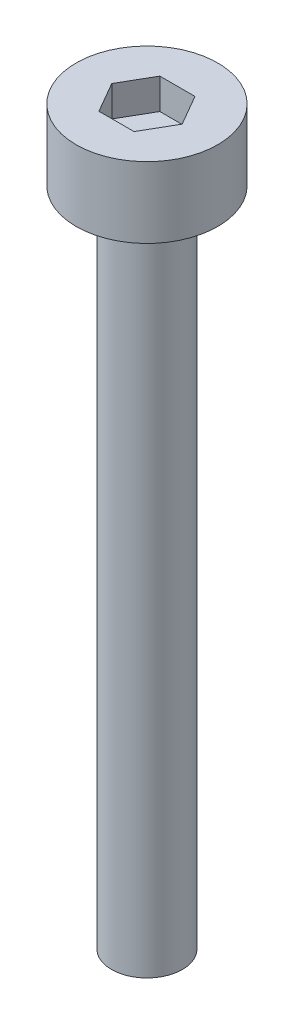
SolidWorks part; units mm, degrees
ref_plane "Front Plane" through (0, 0, 0) normal (0, 0, 1) x (1, 0, 0)
ref_plane "Top Plane" through (0, 0, 0) normal (0, 1, 0) x (1, 0, 0)
ref_plane "Right Plane" through (0, 0, 0) normal (1, 0, 0) x (0, 0, -1)
sketch "Sketch1" plane through (0, 0, 0) normal (0, 1, 0) x (1, 0, 0)
  circle A0 centre (0, 0) radius 1.5
  dimension "D1" = 3
extrude "ScrewShaft" add sketch "Sketch1" along normal blind 28
sketch "Sketch2" plane through (0, 28, 0) normal (0, 1, 0) x (1, 0, 0)
  circle A0 centre (0, 0) radius 3
  dimension "D1" = 6
extrude "Boss-Extrude2" add sketch "Sketch2" along normal blind 3
sketch "Sketch3" plane through (0, 31, 0) normal (0, 1, 0) x (1, 0, 0)
  line L0 (0, 0) -> (0, 1.29) construction
  line L1 (1.4896, 0) -> (0.7448, 1.29)
  line L2 (0.7448, 1.29) -> (-0.7448, 1.29)
  line L3 (-0.7448, 1.29) -> (-1.4896, 0)
  line L4 (-1.4896, 0) -> (-0.7448, -1.29)
  line L5 (-0.7448, -1.29) -> (0.7448, -1.29)
  line L6 (0.7448, -1.29) -> (1.4896, 0)
  circle A0 centre (0, 0) radius 1.29 construction
  dimension "D1" = 2.58
extrude "Cut-Extrude1" cut sketch "Sketch3" against normal blind 1.3
equation "\"X-ROD-SPACING\"=45"
equation "\"Y-ROD-SPACING\"=75"
equation "\"Z-ROD-SPACING\"=17.5"
equation "\"Y-BED-OFFSET\"=2"
equation "\"Y-BED-ROD-INSET\"=3.5"
equation "\"T-SLOT-NUT-FILLET-RADIUS\"=0.5"
equation "\"T-SLOT-SCREW-SHAFT-RADIUS\"=1.55"
equation "\"T-SLOT-SCREW-SHAFT-CUTOUT-LENGTH\"=11"
equation "\"T-SLOT-NUT-DEPTH\"=3.5"
equation "\"T-SLOT-NUT-WIDTH\"=2.85"
equation "\"T-SLOT-NUT-END-DISTANCE\"=8"
equation "\"ACRYLIC-THICKNESS\"=10"
equation "\"ACRYLIC-THICKNESS2\"=4.5"
equation "\"ACRYLIC-TAB-CUTOUT-SIZE\"=\"ACRYLIC-THICKNESS\"+\"ACRYLIC-TAB-TOLERANCE\"*2"
equation "\"ACRYLIC-TAB-WIDTH\"=\"ACRYLIC-THICKNESS\""
equation "\"ACRYLIC-M3-HOLE\"=2.9"
equation "\"SMOOTHROD-CAP-SCREW-DISTANCE\"=20"
equation "\"FRAME-WIDTH-INNER\"=370"
equation "\"NEMA17-HOLE-SPACING\"=31"
equation "\"NEMA17-CENTRAL-CUTOUT\"=22.5"
equation "\"Z-BRACKET-REACH\"=55"
equation "\"TOP-BRACKET-SPACING\"=40"
equation "\"SMOOTHROD-X-LENGTH\"=350"
equation "\"SMOOTHROD-Y-LENGTH\"=350"
equation "\"SMOOTHROD-Z-LENGTH\"=350"
equation "\"SMOOTHROD-TIGHTENING-HEADROOM\"=.25"
equation "\"LEADSCREW-Z-LENGTH\"=300"
equation "\"SCREW-LENGTH-FRAME\"=\"ACRYLIC-THICKNESS\" + 10"
equation "\"SCREW-HEAD-RADIUS\"=6"
equation "\"PRINTED-X-SMOOTHROD-DIAMETER\"=9.0"
equation "\"PRINTED-X-SMOOTHROD-CUTOUT\"=10"
equation "\"PRINTED-X-BASE-HEIGHT\"=10"
equation "\"PRINTED-LM8UU-CUTOUT-SIZE\"=15.5"
equation "\"PRINTED-LM8UU-CUTOUT-LENGTH\"=24.5"
equation "\"PRINTED-X-IDLER-HEIGHT\"=16"
equation "\"PSU-MOUNTING-WIDTH\"=95"
equation "\"PSU-MOUNTING-HEIGHT\"=177"
equation "\"D1@ScrewShaft\"=\"SCREW-LENGTH-EXTRUDER\""
equation "\"D1@Sketch2\"=\"SCREW-HEAD-RADIUS\""
equation "\"Y-BED-SCREW-SPACING\"=209"
equation "\"Y-BED-SCREW-CUTOUT-SLOT-HEIGHT\"=2"
equation "\"Z-ROD-INSET\"=13.5"
equation "\"SCREW-LENGTH-MOTOR\"=\"ACRYLIC-THICKNESS\" + 5"
equation "\"SCREW-LENGTH-EXTRUDER\"=28"
equation "\"Y-BELT-TO-ROD-DISTANCE\"=20"
equation "\"SPOOL-HOLDER-ROD-SPACING\"=150"
equation "\"ACRYLIC-X-CARRIAGE-WIDTH\"=55"
equation "\"ACRYLIC-X-CARRIAGE-HEIGHT\"=75"
equation "\"ACRYLIC-X-CARRIAGE-CENTER-TAB-SPACING\"=14"
